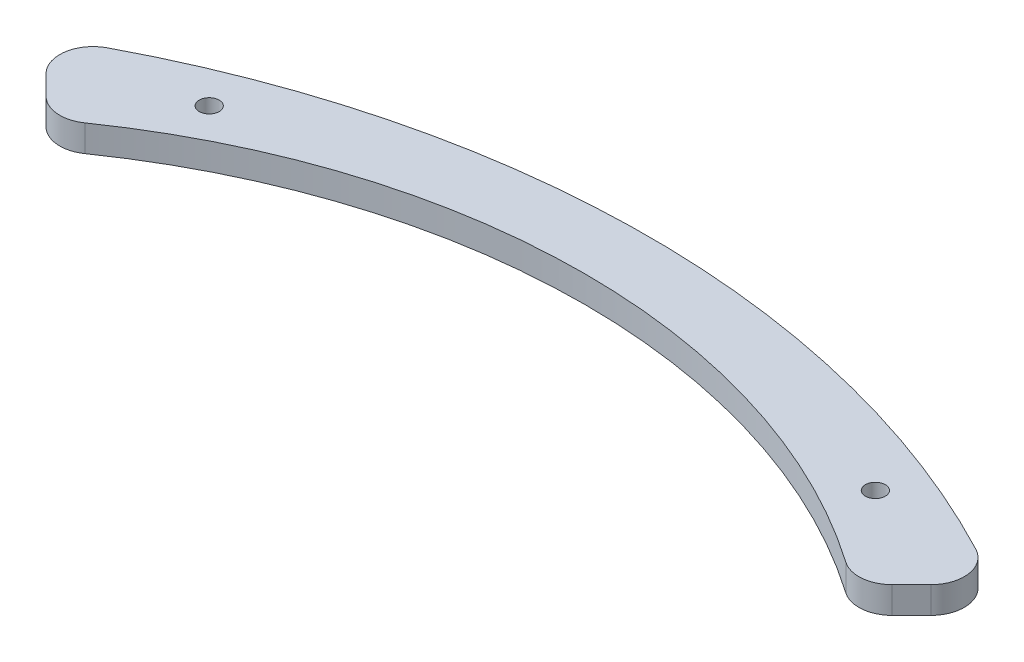
SolidWorks part; units mm, degrees
material "1060 Alloy"
ref_plane "Front Plane" through (0, 0, 0) normal (0, 0, 1) x (1, 0, 0)
ref_plane "Top Plane" through (0, 0, 0) normal (0, 1, 0) x (1, 0, 0)
ref_plane "Right Plane" through (0, 0, 0) normal (1, 0, 0) x (0, 0, -1)
sketch "Sketch1" plane through (0, 0, 0) normal (0, 1, 0) x (1, 0, 0)
  line L0 (-71.1027, 120.6002) -> (-60.4961, 109.9936)
  line L1 (71.1027, 120.6002) -> (60.4961, 109.9936)
  line L3 (0, 0) -> (-117.9329, 117.9329) construction
  line L4 (0, 0) -> (118.2874, 118.2874) construction
  line L5 (0, 0) -> (0, 174.1104) construction
  line L6 (-15, 129.1317) -> (15, 129.1317) construction
  line L7 (-15, 129.1317) -> (-15, 118.1317) construction
  line L8 (-15, 118.1317) -> (15, 118.1317) construction
  line L9 (15, 129.1317) -> (15, 118.1317) construction
  arc A0 (-71.1027, 120.6002) -> (71.1027, 120.6002) centre (0, 0) cw
  arc A1 (-60.4961, 109.9936) -> (60.4961, 109.9936) centre (0, 30.3681) cw
  circle A2 centre (0, 0) radius 130 construction
  dimension "D1" = 140
  dimension "D6" = 100
  dimension "D7" = 10
  dimension "D2" = 15
  dimension "D3" = 45
  dimension "D4" = 35
  dimension "D5" = 35
  dimension "D8" = 11
  dimension "D9" = 30
extrude "Boss-Extrude1" add sketch "Sketch1" along normal blind 4
fillet "Fillet1" radius 5 4 edges at (71.1027, 2, -120.6002) (60.4961, 2, -109.9936) (-71.1027, 2, -120.6002) (-60.4961, 2, -109.9936)
sketch "Sketch2" plane through (0, 4, 0) normal (0, 1, 0) x (1, 0, 0)
  circle A0 centre (-50, 124) radius 1.5
  circle A1 centre (50, 124) radius 1.5
  dimension "D1" = 3
  dimension "D2" = 124
  dimension "D3" = 50
  dimension "D4" = 50
extrude "Cut-Extrude1" cut sketch "Sketch2" against normal up to next
